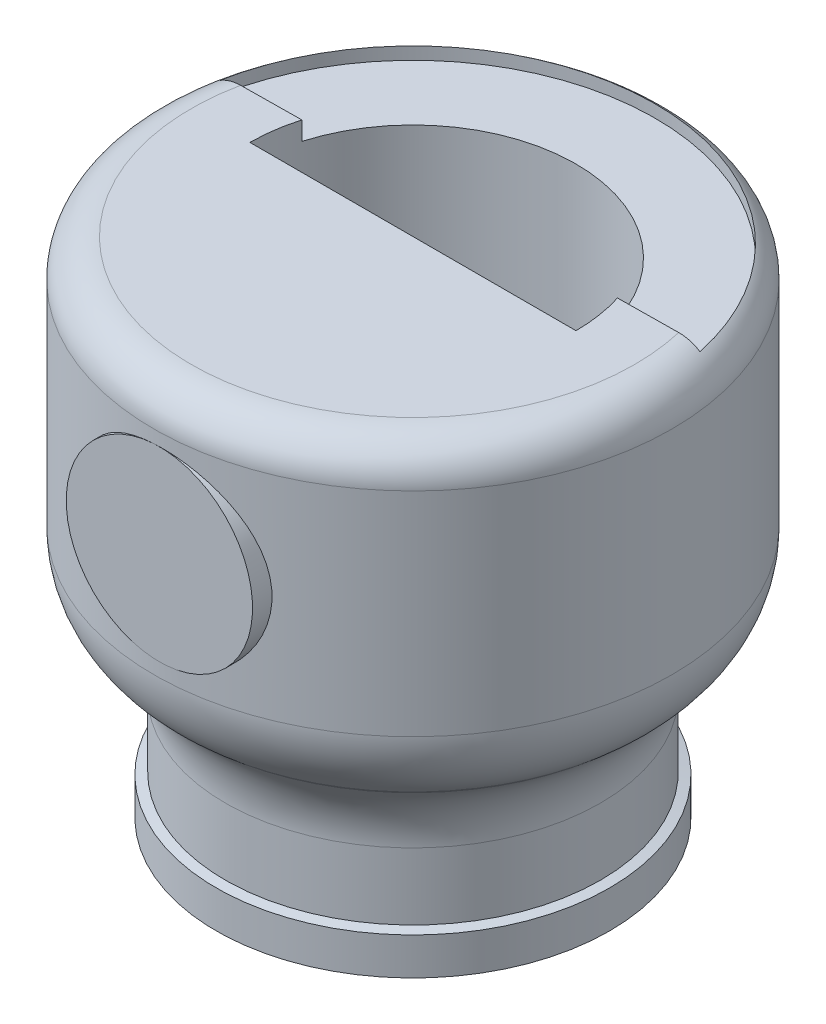
SolidWorks part; units mm, degrees
ref_plane "Front Plane" through (0, 0, 0) normal (0, 0, 1) x (1, 0, 0)
ref_plane "Top Plane" through (0, 0, 0) normal (0, 1, 0) x (1, 0, 0)
ref_plane "Right Plane" through (0, 0, 0) normal (1, 0, 0) x (0, 0, -1)
sketch "Sketch1" plane through (0, 0, 0) normal (0, 0, 1) x (1, 0, 0)
  line L0 (2.7649, 7.8218) -> (2.7649, 58.3592) construction
  line L1 (20.9, 0) -> (23.8716, 0)
  line L2 (23.8716, 0) -> (23.8716, 4)
  line L3 (23.8716, 4) -> (22.9, 4.2367)
  line L4 (22.9, 4.2367) -> (22.9, 11.4043)
  line L6 (20.9, 0) -> (20.9, 14)
  line L12 (19.9, 15) -> (2.7649, 15)
  line L17 (26.4721, 19.0648) -> (26.9883, 19.4979)
  line L18 (30.5604, 27.1583) -> (30.5604, 50)
  line L20 (26.5604, 54) -> (2.7649, 54)
  line L22 (2.7649, 15) -> (2.7649, 54)
  arc A1 (30.5604, 50) -> (26.5604, 54) centre (26.5604, 50) ccw
  arc A2 (26.4721, 19.0648) -> (22.9, 11.4043) centre (32.9, 11.4043) ccw
  arc A3 (26.9883, 19.4979) -> (30.5604, 27.1583) centre (20.5604, 27.1583) ccw
  arc A6 (20.9, 14) -> (19.9, 15) centre (19.9, 14) ccw
  point P11 (22.9, 54)
  point P28 (28.5604, 23.4279)
  point P31 (20.9, 17)
  dimension "D9" = 4
  dimension "D16" = 10
  dimension "D19" = 1
  dimension "D2" = 4
  dimension "D3" = 1
  dimension "D6" = 2
  dimension "D7" = 2.9716
  dimension "D11" = 15
  dimension "D15" = 10
revolve "Revolve1" add sketch "Sketch1" angle 360 about L0
ref_plane "Plane1" through (0, 4, 0) normal (0, 1, 0) x (1, 0, 0)
sketch "Sketch3" plane through (0, 0, 0) normal (0, 0, 1) x (1, 0, 0)
  point P0 (1.2404, 19.1989)
ref_point "Point1"
ref_plane "Plane2" through (0, 0, 22.9) normal (0, 0, 1) x (1, 0, 0)
ref_plane "Plane3" through (0, 0, 27.7955) normal (0, 0, 1) x (1, 0, 0)
ref_plane "Plane4" through (0, 54, 0) normal (0, 1, 0) x (1, 0, 0)
sketch "Sketch9" plane through (0, 54, 0) normal (0, 1, 0) x (1, 0, 0)
  line L0 (-22.7913, 4.7834) -> (28.2054, 5.3648)
  arc A0 (28.2054, 5.3648) -> (-22.7913, 4.7834) centre (2.7649, 0) ccw
  circle A3 centre (2.7649, 0) radius 23.7955 construction
  point P1 (24.8418, 13.7335)
  dimension "D1" = 51
  dimension "D3" = 26
  dimension "D4" = 0
sketch "Sketch10" plane through (0, 0, 27.7955) normal (0, 0, 1) x (1, 0, 0)
  line L0 (30.5604, 27.1583) -> (-25.0306, 27.1583) construction
  circle A0 centre (3.3463, 38.6583) radius 10
  dimension "D1" = 20
  dimension "D2" = 11.5
extrude "Boss-Extrude1" add sketch "Sketch10" against normal blind 5
ref_plane "Plane5" through (0, 17, 0) normal (0, 1, 0) x (1, 0, 0)
sketch "Sketch11" plane through (0, 17, 0) normal (0, 1, 0) x (1, 0, 0)
  line L0 (-14.7351, 0) -> (20.2649, 0)
  arc A1 (-14.7351, 0) -> (20.2649, 0) centre (2.7649, 0) cw
  circle A2 centre (2.7649, 0) radius 20.9233 construction
  dimension "D2" = 0
  dimension "D1" = 35
extrude "Cut-Extrude3" cut sketch "Sketch11" against normal blind 20 and the other way blind 45
ref_plane "Plane6" through (0, 0, -27.7955) normal (0, 0, -1) x (-1, 0, 0)
sketch "Sketch12" plane through (0, 0, 27.7955) normal (0, 0, 1) x (1, 0, 0)
  line L0 (30.5604, 50) -> (-25.0306, 50) construction
  line L1 (-26.9971, 52.5) -> (33.0029, 52.5)
  line L2 (-26.9971, 52.5) -> (-26.9971, 49.5)
  line L3 (-26.9971, 49.5) -> (33.0029, 49.5)
  line L4 (33.0029, 52.5) -> (33.0029, 49.5)
  line L5 (-26.9971, 52.5) -> (33.0029, 49.5) construction
  line L6 (-26.9971, 49.5) -> (33.0029, 52.5) construction
  point P0 (3.0029, 51)
  dimension "D1" = 3
  dimension "D2" = 1
  dimension "D3" = 60
extrude "Cut-Extrude5" cut sketch "Sketch9" against normal blind 2
